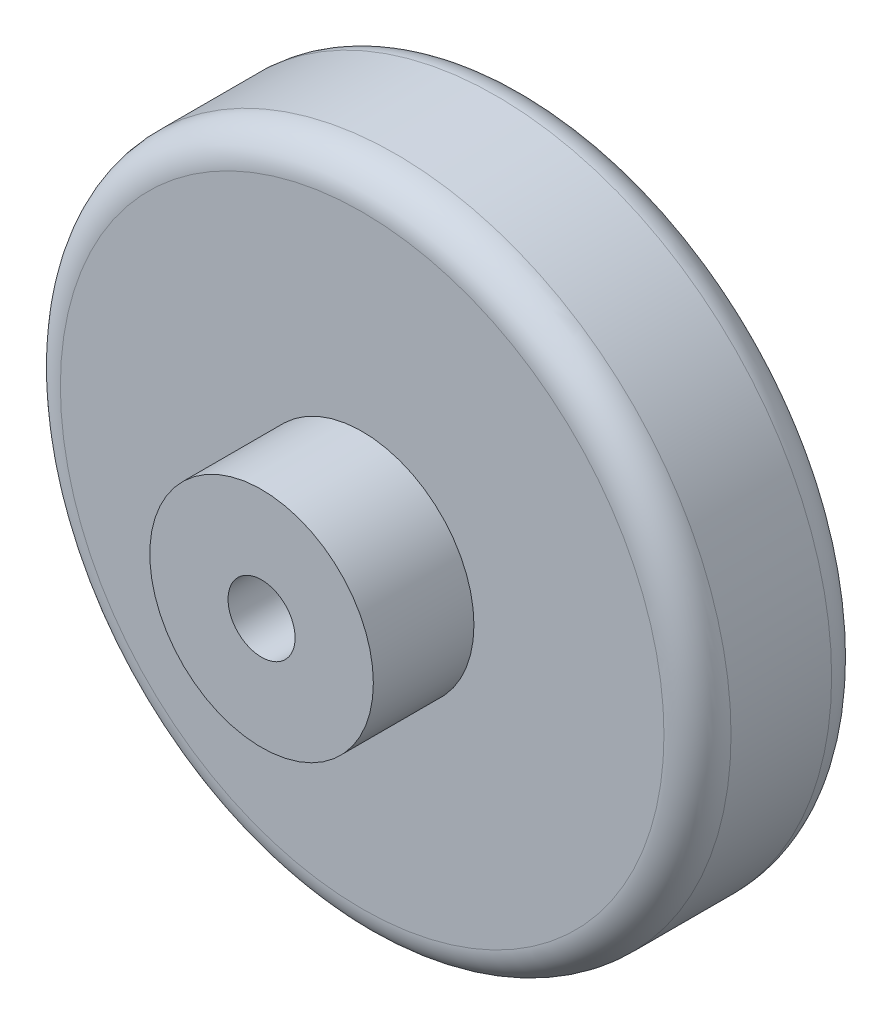
SolidWorks part; units mm, degrees
ref_plane "Front Plane" through (0, 0, 0) normal (0, 0, 1) x (1, 0, 0)
ref_plane "Top Plane" through (0, 0, 0) normal (0, 1, 0) x (1, 0, 0)
ref_plane "Right Plane" through (0, 0, 0) normal (1, 0, 0) x (0, 0, -1)
sketch "Sketch1" plane through (0, 0, 0) normal (0, 0, 1) x (1, 0, 0)
  circle A0 centre (0, 0) radius 30
  dimension "D1" = 60
extrude "Boss-Extrude1" add sketch "Sketch1" along normal blind 15
sketch "Sketch2" plane through (0, 0, 15) normal (0, 0, 1) x (1, 0, 0)
  circle A0 centre (0, 0) radius 10
  dimension "D1" = 20
extrude "Boss-Extrude2" add sketch "Sketch2" along normal blind 9
sketch "Sketch3" plane through (0, 0, 24) normal (0, 0, 1) x (1, 0, 0)
  circle A0 centre (0, 0) radius 3
  dimension "D1" = 6
extrude "Cut-Extrude1" cut sketch "Sketch3" against normal through all
fillet "Fillet1" radius 3 2 edges at (30, 0, 0) (30, 0, 15)
sketch "Sketch4" plane through (0, 0, 0) normal (0, 0, -1) x (-1, 0, 0)
  circle A0 centre (0, 0) radius 6
  dimension "D1" = 12
extrude "Cut-Extrude2" cut sketch "Sketch4" against normal blind 4
fillet "Fillet2" radius 1 1 edges at (-6, 0, 0)
